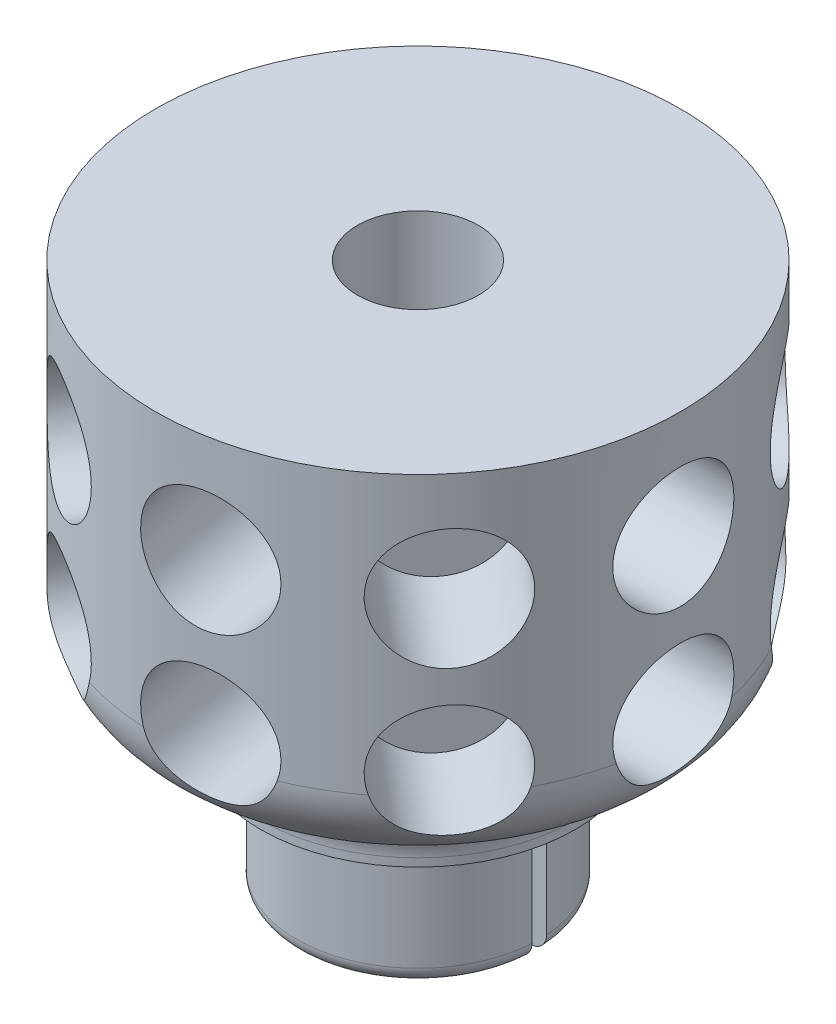
SolidWorks part; units mm, degrees
ref_plane "Front Plane" through (0, 0, 0) normal (0, 0, 1) x (1, 0, 0)
ref_plane "Top Plane" through (0, 0, 0) normal (0, 1, 0) x (1, 0, 0)
ref_plane "Right Plane" through (0, 0, 0) normal (1, 0, 0) x (0, 0, -1)
sketch "Sketch1" plane through (0, 0, 0) normal (0, 1, 0) x (1, 0, 0)
  circle A0 centre (0, 0) radius 32.5
  dimension "D1" = 65
extrude "Boss-Extrude1" add sketch "Sketch1" along normal blind 44.3
sketch "Sketch3" plane through (0, 0, 0) normal (0, -1, 0) x (1, 0, 0)
  circle A0 centre (0, 0) radius 19.5
  dimension "D1" = 39
extrude "Boss-Extrude2" add sketch "Sketch3" along normal blind 7
sketch "Sketch4" plane through (0, -7, 0) normal (0, -1, 0) x (1, 0, 0)
  circle A0 centre (0, 0) radius 15.05
  dimension "D1" = 30.1
extrude "Boss-Extrude3" add sketch "Sketch4" along normal blind 16
fillet "Fillet1" radius 6 1 edges at (0, 0, -19.5)
sketch "Sketch7" plane through (0, -23, 0) normal (0, -1, 0) x (1, 0, 0)
  line L1 (33.0968, 0.9034) -> (-33.0968, 0.9034)
  line L2 (33.0968, 0.9034) -> (33.0968, -0.9034)
  line L3 (33.0968, -0.9034) -> (-33.0968, -0.9034)
  line L4 (-33.0968, 0.9034) -> (-33.0968, -0.9034)
  line L5 (33.0968, 0.9034) -> (-33.0968, -0.9034) construction
  line L6 (33.0968, -0.9034) -> (-33.0968, 0.9034) construction
  point P0 (0, 0)
extrude "Cut-Extrude2" cut sketch "Sketch7" against normal up to surface (16 mm away) up to face at (0, -7, -15.05)
fillet "Fillet2" radius 2 2 edges at (0, -23, 15.05) (0, -23, -15.05)
sketch "Sketch11" plane through (0, 44.3, 0) normal (0, 1, 0) x (1, 0, 0)
  line L0 (0, 0) -> (0, -50000) construction
  line L6 (3.4, 32.3217) -> (-3.4, 32.3217)
  line L7 (3.4, 32.3217) -> (3.4, 23.3217)
  line L8 (3.4, 23.3217) -> (-3.4, 23.3217)
  line L9 (-3.4, 32.3217) -> (-3.4, 23.3217)
  circle A2 centre (0, 0) radius 32.5 construction
  dimension "D1" = 6.8
  dimension "D2" = 9
extrude "Boss-Extrude4" add sketch "Sketch11" against normal up to next (44.3 mm away)
ref_plane "Plane1" through (32.5, 0, 0) normal (1, 0, 0) x (0, 0, -1)
sketch "Sketch14" plane through (32.5, 0, 0) normal (1, 0, 0) x (0, 0, -1)
  line L0 (-32.5, 0) -> (32.5, 0) construction
  circle A0 centre (0, 12) radius 7.5
  circle A1 centre (0, 30.9111) radius 7.5
  dimension "D1" = 15
  dimension "D2" = 12
extrude "Cut-Extrude6" cut sketch "Sketch14" against normal blind 14
pattern_circular "CirPattern4" count 9 over 360 about axis through (0, 44.3, 0) along (0, -1, 0) of "Cut-Extrude6" reverse direction yes
fillet "Fillet3" radius 10 1 edges at (0, 0, 32.5)
sketch "Sketch15" plane through (0, 44.3, 0) normal (0, 1, 0) x (1, 0, 0)
  circle A0 centre (0, 0) radius 7.5
  dimension "D1" = 15
extrude "Cut-Extrude7" cut sketch "Sketch15" against normal through all
